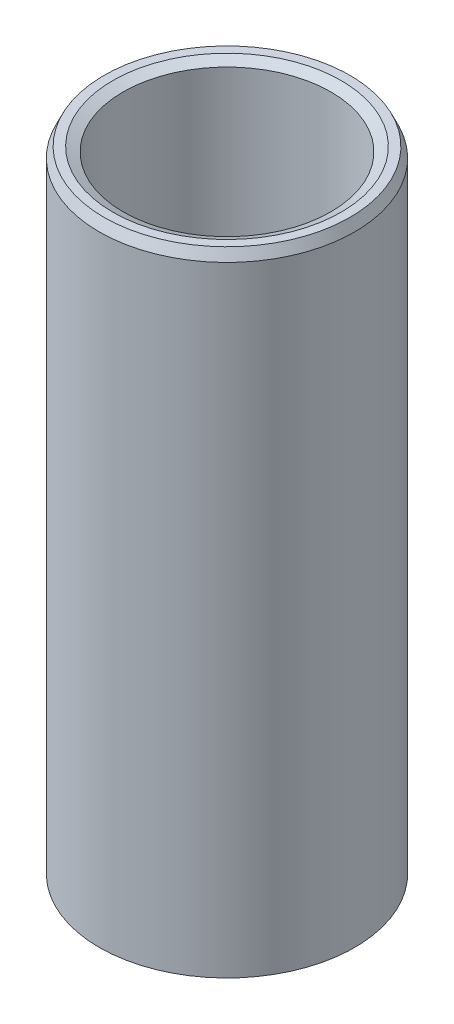
SolidWorks part; units mm, degrees
ref_plane "Front Plane" through (0, 0, 0) normal (0, 0, 1) x (1, 0, 0)
ref_plane "Top Plane" through (0, 0, 0) normal (0, 1, 0) x (1, 0, 0)
ref_plane "Right Plane" through (0, 0, 0) normal (1, 0, 0) x (0, 0, -1)
sketch "Sketch1" plane through (0, 0, 0) normal (0, 1, 0) x (1, 0, 0)
  circle A0 centre (0, 0) radius 25
  dimension "SLEEVE_OD" = 50
extrude "Boss-Extrude1" add sketch "Sketch1" along normal blind 124.195
sketch "Sketch2" plane through (0, 0, 0) normal (0, 1, 0) x (1, 0, 0)
  circle A0 centre (0, 0) radius 20.332
  dimension "BORE_D" = 40.664
extrude "Cut-Extrude1" cut sketch "Sketch2" along normal through all
chamfer "Chamfer1" distance 1.9988 angle 25.004 4 edges at (0, 124.195, 20.332) (0, 0, 20.332) (0, 0, 25) (0, 124.195, 25) first distance on face at (0, 124.195, 20.332) first distance on face at (0, 0, 20.332) first distance on face at (0, 124.195, 25)
